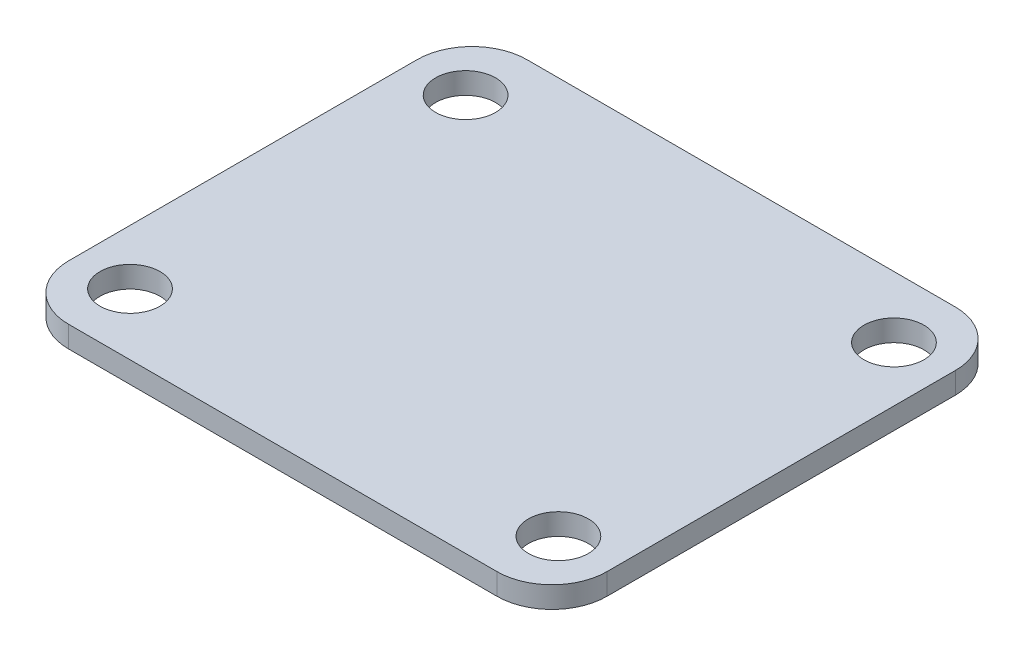
SolidWorks part; units mm, degrees
ref_plane "Front Plane" through (0, 0, 0) normal (0, 0, 1) x (1, 0, 0)
ref_plane "Top Plane" through (0, 0, 0) normal (0, 1, 0) x (1, 0, 0)
ref_plane "Right Plane" through (0, 0, 0) normal (1, 0, 0) x (0, 0, -1)
sketch "Sketch1" plane through (0, 0, 0) normal (0, 1, 0) x (1, 0, 0)
  line L0 (-18.85, 0) -> (18.85, 0) construction
  line L1 (-18.85, 16.05) -> (18.85, 16.05)
  line L2 (-18.85, 16.05) -> (-18.85, -16.05)
  line L3 (-18.85, -16.05) -> (18.85, -16.05)
  line L4 (18.85, 16.05) -> (18.85, -16.05)
  line L5 (0, 16.05) -> (0, -16.05) construction
  line L6 (15, 11.75) -> (15, -11.75) construction
  line L9 (15, 11.75) -> (-15, 11.75) construction
  line L10 (-15, 11.75) -> (-15, -11.75) construction
  line L11 (15, -11.75) -> (-15, -11.75) construction
  circle A0 centre (15, 11.75) radius 2.1
  circle A1 centre (15, -11.75) radius 2.1
  circle A2 centre (-15, 11.75) radius 2.1
  circle A3 centre (-15, -11.75) radius 2.1
  point P8 (0, 0)
  point P16 (15, 0)
  point P22 (0, 11.75)
  dimension "D4" = 4.2
  dimension "D1" = 32.1
  dimension "D2" = 37.7
  dimension "D3" = 23.5
  dimension "D5" = 30
extrude "Boss-Extrude1" add sketch "Sketch1" along normal blind 1.5
fillet "Fillet1" radius 3.85 4 edges at (-18.85, 0.75, -16.05) (18.85, 0.75, -16.05) (-18.85, 0.75, 16.05) (18.85, 0.75, 16.05)
sketch "Sketch2" plane through (0, 0, 0) normal (1, 0, 0) x (0, 0, -1)
  line L0 (0, 0) -> (0, -2.5)
  line L1 (-12.2, 0) -> (12.2, 0) construction
  line L2 (0, 0) -> (-16.05, 0)
  line L3 (0, -2.5) -> (-13.0706, -2.5)
  line L4 (-13.0706, -2.5) -> (-16.05, 0)
  dimension "D1" = 40
  dimension "D2" = 2.5
revolve "Revolve1" add sketch "Sketch2" angle 360 about L0
ref_axis "Axis1" through (0, 0, 0) along (0, -1, 0)
